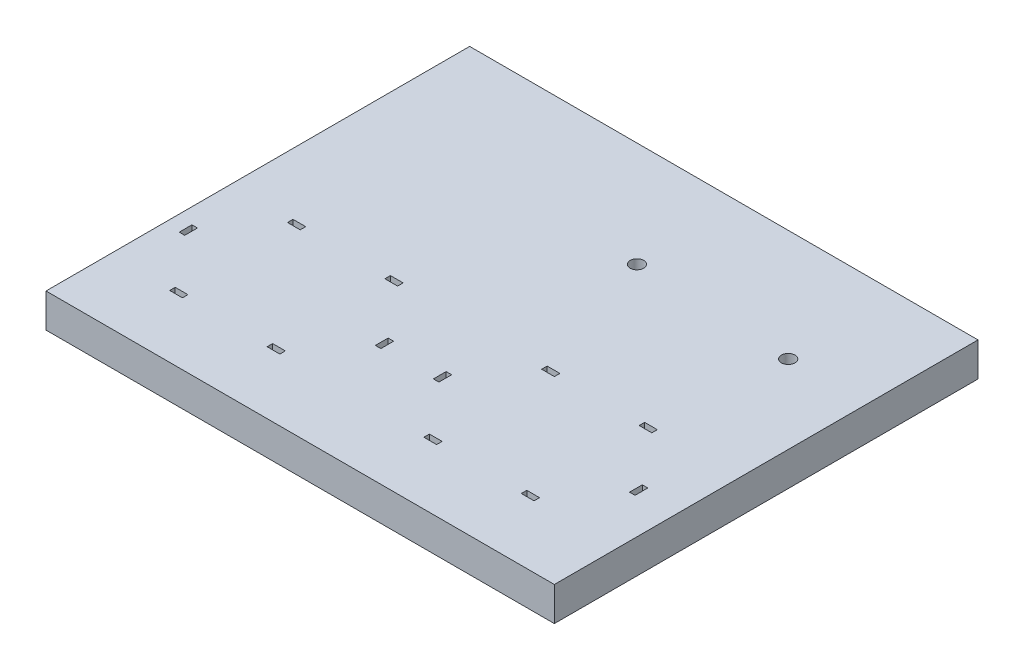
SolidWorks part; units mm, degrees
ref_plane "Front Plane" through (0, 0, 0) normal (0, 0, 1) x (1, 0, 0)
ref_plane "Top Plane" through (0, 0, 0) normal (0, 1, 0) x (1, 0, 0)
ref_plane "Right Plane" through (0, 0, 0) normal (1, 0, 0) x (0, 0, -1)
sketch "Sketch1" plane through (0, 0, 0) normal (0, 1, 0) x (1, 0, 0)
  line L0 (-66.0627, 0) -> (65.2437, 0) construction
  line L1 (-60, 50) -> (60, 50)
  line L2 (-60, 50) -> (-60, -50)
  line L3 (-60, -50) -> (60, -50)
  line L4 (60, 50) -> (60, -50)
  line L5 (27.5, -7.5) -> (27.5, -34) construction
  line L6 (45, 10) -> (-18.5, 10) construction
  line L7 (45, 10) -> (45, 35) construction
  line L8 (45, 35) -> (-18.5, 35) construction
  line L9 (-18.5, 10) -> (-18.5, 35) construction
  line L10 (5, -7.5) -> (50, -7.5) construction
  line L11 (5, -7.5) -> (5, -34) construction
  line L12 (5, -34) -> (50, -34) construction
  line L13 (50, -7.5) -> (50, -34) construction
  line L14 (5, -20.75) -> (50, -20.75) construction
  line L15 (40.5, -7.5) -> (37.5, -7.5)
  line L16 (14.5, -7.5) -> (17.5, -7.5)
  line L17 (14.5, -7.5) -> (14.5, -6.2)
  line L18 (14.5, -6.2) -> (17.5, -6.2)
  line L19 (17.5, -7.5) -> (17.5, -6.2)
  line L20 (5, -19.25) -> (3.7, -19.25)
  line L21 (5, -19.25) -> (5, -22.25)
  line L22 (5, -22.25) -> (3.7, -22.25)
  line L23 (3.7, -19.25) -> (3.7, -22.25)
  line L24 (37.5, -7.5) -> (37.5, -6.2)
  line L25 (40.5, -6.2) -> (37.5, -6.2)
  line L26 (40.5, -7.5) -> (40.5, -6.2)
  line L27 (50, -19.25) -> (51.3, -19.25)
  line L28 (51.3, -19.25) -> (51.3, -22.25)
  line L29 (50, -22.25) -> (51.3, -22.25)
  line L30 (50, -19.25) -> (50, -22.25)
  line L31 (37.5, -34) -> (37.5, -35.3)
  line L32 (40.5, -34) -> (37.5, -34)
  line L33 (40.5, -34) -> (40.5, -35.3)
  line L34 (40.5, -35.3) -> (37.5, -35.3)
  line L35 (14.5, -34) -> (17.5, -34)
  line L36 (17.5, -34) -> (17.5, -35.3)
  line L37 (14.5, -34) -> (14.5, -35.3)
  line L38 (14.5, -35.3) -> (17.5, -35.3)
  line L39 (-2.5, -65.1553) -> (-2.5, 67.8606) construction
  line L46 (-19.5, -35.3) -> (-22.5, -35.3)
  line L47 (-19.5, -34) -> (-19.5, -35.3)
  line L48 (-22.5, -34) -> (-22.5, -35.3)
  line L49 (-19.5, -34) -> (-22.5, -34)
  line L50 (-45.5, -35.3) -> (-42.5, -35.3)
  line L51 (-45.5, -34) -> (-45.5, -35.3)
  line L52 (-45.5, -34) -> (-42.5, -34)
  line L53 (-42.5, -34) -> (-42.5, -35.3)
  line L54 (-55, -19.25) -> (-55, -22.25)
  line L55 (-55, -22.25) -> (-56.3, -22.25)
  line L56 (-56.3, -19.25) -> (-56.3, -22.25)
  line L57 (-55, -19.25) -> (-56.3, -19.25)
  line L58 (-45.5, -7.5) -> (-45.5, -6.2)
  line L59 (-45.5, -6.2) -> (-42.5, -6.2)
  line L60 (-42.5, -7.5) -> (-42.5, -6.2)
  line L61 (-8.7, -19.25) -> (-8.7, -22.25)
  line L62 (-10, -22.25) -> (-8.7, -22.25)
  line L63 (-10, -19.25) -> (-10, -22.25)
  line L64 (-10, -19.25) -> (-8.7, -19.25)
  line L65 (-22.5, -7.5) -> (-22.5, -6.2)
  line L66 (-19.5, -6.2) -> (-22.5, -6.2)
  line L67 (-19.5, -7.5) -> (-19.5, -6.2)
  line L68 (-19.5, -7.5) -> (-22.5, -7.5)
  line L69 (-45.5, -7.5) -> (-42.5, -7.5)
  circle A0 centre (41.5, 23.7) radius 1.6
  circle A1 centre (4.3, 25.2) radius 1.6
  point P4 (60, 0)
  point P6 (0, 50)
  point P33 (5, -20.75)
  dimension "D5" = 3.2
  dimension "D10" = 3.2
  dimension "D17" = 3
  dimension "D18" = 1.3
  dimension "D1" = 120
  dimension "D2" = 100
  dimension "D3" = 10
  dimension "D4" = 15
  dimension "D6" = 3.5
  dimension "D7" = 13.7
  dimension "D8" = 63.5
  dimension "D9" = 25
  dimension "D11" = 40.7
  dimension "D12" = 15.2
  dimension "D13" = 26.5
  dimension "D14" = 45
  dimension "D15" = 7.5
  dimension "D16" = 15
  dimension "D19" = 3
  dimension "D20" = 1.3
  dimension "D21" = 20
  dimension "D22" = 10
extrude "Boss-Extrude1" add sketch "Sketch1" along normal blind 8
